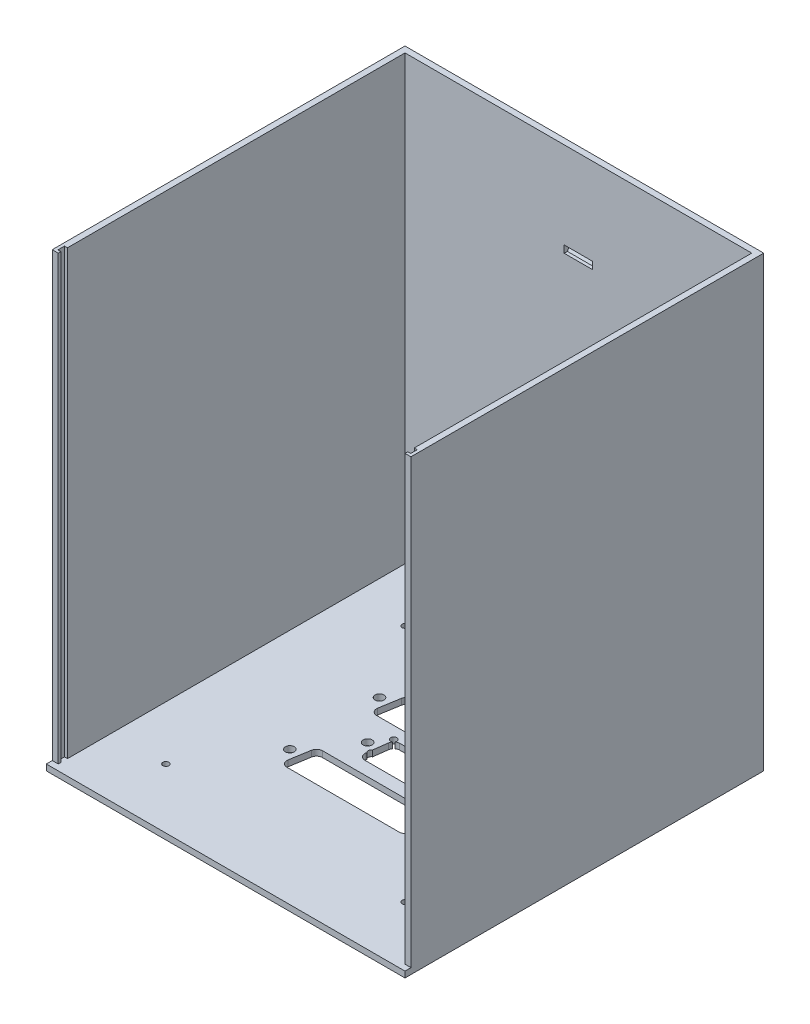
SolidWorks part; units mm, degrees
other "Markup1"
sketch "Sketch8" plane through (60, 0, -60) normal (0.7052, -0.7014, -0.1039) x (0.274, 0.4048, -0.8724)
other "Markup2"
sketch "Sketch9" plane through (60, 0, -60) normal (0.9922, -0.0018, -0.1244) x (-0.0942, 0.6423, -0.7606)
ref_plane "Front Plane" through (0, 0, 0) normal (0, 0, 1) x (1, 0, 0)
ref_plane "Top Plane" through (0, 0, 0) normal (0, 1, 0) x (1, 0, 0)
ref_plane "Right Plane" through (0, 0, 0) normal (1, 0, 0) x (0, 0, -1)
sketch "Sketch1" plane through (0, 0, 0) normal (0, 1, 0) x (1, 0, 0)
  line L5 (-60, 60) -> (60, 60)
  line L6 (-60, 60) -> (-60, -60)
  line L7 (-60, -60) -> (60, -60)
  line L8 (60, 60) -> (60, -60)
  dimension "D1" = 120
  dimension "D2" = 120
  dimension "D3" = 60
  dimension "D4" = 60
extrude "Main-Body" add sketch "Sketch1" along normal blind 150
sketch "Sketch11" plane through (0, 150, 0) normal (0, 1, 0) x (1, 0, 0)
  line L0 (-60, 60) -> (-60, -60) construction
  line L1 (58, -60) -> (-58, -60)
  line L2 (58, -60) -> (58, 58)
  line L3 (58, 58) -> (-58, 58)
  line L4 (-58, -60) -> (-58, 58)
  line L5 (58, -60) -> (-58, 58) construction
  line L6 (58, 58) -> (-58, -60) construction
  line L13 (60, 60) -> (-60, 60) construction
  point P0 (0, -1)
  dimension "D1" = 116
  dimension "D2" = 118
  dimension "D6" = 2
  dimension "D7" = 2
extrude "Hollow" cut sketch "Sketch11" against normal blind 148
sketch "Sketch12" plane through (0, 150, 0) normal (0, 1, 0) x (1, 0, 0)
  line L0 (-60, 60) -> (-60, -60) construction
  line L1 (-58, -60) -> (-60, -60)
  line L2 (-58, -60) -> (-58, -58)
  line L3 (-58, -58) -> (-60, -58)
  line L4 (-60, -60) -> (-60, -58)
  dimension "D1" = 2
extrude "Lid-Cut" cut sketch "Sketch12" against normal blind 148
mirror "Mirror-Lid-Cut" about plane through (0, 0, 0) normal (1, 0, 0) of "Lid-Cut"
sketch "Sketch13" plane through (0, 150, 0) normal (0, 1, 0) x (1, 0, 0)
  line L0 (-58, 58) -> (-58, -58) construction
  line L1 (-58, -57.1) -> (-59, -57.1)
  line L2 (-58, -57.1) -> (-58, -54.9)
  line L3 (-58, -54.9) -> (-59, -54.9)
  line L4 (-59, -57.1) -> (-59, -54.9)
  line L5 (-58, -58) -> (-60, -58) construction
  dimension "D1" = 1
  dimension "D2" = 0.9
  dimension "D3" = 2.2
extrude "Rail-Cut" cut sketch "Sketch13" against normal blind 148
sketch "Sketch2" plane through (0, 0, 0) normal (0, -1, 0) x (1, 0, 0)
  circle A0 centre (-40, 40) radius 1
  circle A1 centre (40, 40) radius 1
  circle A2 centre (40, -40) radius 1
  circle A3 centre (-40, -40) radius 1
  dimension "D1" = 40
  dimension "D3" = 2
  dimension "D2" = 40
  dimension "D4" = 2
  dimension "D5" = 2
extrude "Main-PCB-Holes" cut sketch "Sketch2" against normal up to next
sketch "Sketch3" plane through (0, 150, 0) normal (0, 1, 0) x (1, 0, 0)
  line L0 (-9, 5.23) -> (9, 5.23) construction
  circle A0 centre (-9, 5.23) radius 1.05
  circle A1 centre (9, 5.23) radius 1.05
  circle A2 centre (9, -2.27) radius 1.05
  circle A3 centre (-9, -2.27) radius 1.05
  dimension "D1" = 9
  dimension "D3" = 2.1
  dimension "D2" = 5.23
  dimension "D4" = 2
  dimension "D6" = 18
  dimension "D7" = 7.5
  dimension "D5" = 2
extrude "LED-PCB-Holes" cut sketch "Sketch3" against normal up to next
sketch "Sketch4" plane through (0, 0, 0) normal (0, -1, 0) x (1, 0, 0)
  line L0 (-12.5, 0) -> (12.5, 0) construction
  line L1 (-23.52, -15) -> (23.52, -15) construction
  line L2 (-6.8916, -5.1179) -> (6.8916, -5.1179)
  line L4 (-7.7666, 5.6321) -> (7.7666, 5.6321)
  line L6 (-17.6522, -20.0462) -> (17.6522, -20.0462)
  line L8 (-18.7772, -9.2962) -> (18.7772, -9.2962)
  line L10 (-23.52, 15) -> (23.52, 15) construction
  line L11 (-17.6522, 9.9538) -> (17.6522, 9.9538)
  line L13 (-18.7772, 20.7038) -> (18.7772, 20.7038)
  line L16 (-19.625, 11.625) -> (-20.75, 18.375)
  line L19 (20.75, 18.375) -> (19.625, 11.625)
  line L22 (-8.875, -3.375) -> (-9.75, 3.375)
  line L25 (9.75, 3.375) -> (8.875, -3.375)
  line L28 (-20.75, -11.625) -> (-19.625, -18.375)
  line L31 (19.625, -18.375) -> (20.75, -11.625)
  circle A0 centre (-12.5, 0) radius 1.5
  circle A1 centre (12.5, 0) radius 1.5
  circle A2 centre (-23.52, -15) radius 1.5
  circle A3 centre (23.52, -15) radius 1.5
  circle A4 centre (-23.52, 15) radius 1.5
  circle A5 centre (23.52, 15) radius 1.5
  arc A6 (18.7772, 20.7038) -> (20.75, 18.375) centre (18.7772, 18.7038) cw
  arc A7 (-18.7772, 20.7038) -> (-20.75, 18.375) centre (-18.7772, 18.7038) ccw
  arc A8 (17.6522, 9.9538) -> (19.625, 11.625) centre (17.6522, 11.9538) ccw
  arc A9 (-17.6522, 9.9538) -> (-19.625, 11.625) centre (-17.6522, 11.9538) cw
  arc A10 (20.75, -11.625) -> (18.7772, -9.2962) centre (18.7772, -11.2962) ccw
  arc A11 (17.6522, -20.0462) -> (19.625, -18.375) centre (17.6522, -18.0462) ccw
  arc A12 (-19.625, -18.375) -> (-17.6522, -20.0462) centre (-17.6522, -18.0462) ccw
  arc A13 (-20.75, -11.625) -> (-18.7772, -9.2962) centre (-18.7772, -11.2962) cw
  arc A14 (7.7666, 5.6321) -> (9.75, 3.375) centre (7.7666, 3.6321) cw
  arc A15 (8.875, -3.375) -> (6.8916, -5.1179) centre (6.8916, -3.1179) cw
  arc A16 (-8.875, -3.375) -> (-6.8916, -5.1179) centre (-6.8916, -3.1179) ccw
  arc A17 (-9.75, 3.375) -> (-7.7666, 5.6321) centre (-7.7666, 3.6321) cw
  point P4 (0, 0)
  point P12 (0, 5.6321)
  point P17 (0, -15)
  point P24 (0, -20.0462)
  point P29 (0, 15)
  point P32 (0, -5.1179)
  point P34 (0, 9.9538)
  point P35 (0, 20.7038)
  point P36 (0, -9.2962)
  point P38 (20.1875, -15)
  point P41 (9.3125, 0)
  point P42 (20.1875, 15)
  point P52 (21.1381, 20.7038)
  point P59 (19.3465, 9.9538)
  point P66 (21.1381, -9.2962)
  point P69 (19.3465, -20.0462)
  point P76 (10.0426, 5.6321)
  point P79 (8.6491, -5.1179)
  dimension "D1" = 3
  dimension "D2" = 3
  dimension "D8" = 3
  dimension "D7" = 3
  dimension "D14" = 3
  dimension "D15" = 3
  dimension "D4" = 41.5
  dimension "D21" = 2
  dimension "D25" = 2
  dimension "D27" = 2
  dimension "D3" = 25
  dimension "D6" = 10.75
  dimension "D9" = 47.04
  dimension "D13" = 15
  dimension "D16" = 47.04
  dimension "D18" = 10.75
  dimension "D19" = 15
  dimension "D20" = 10.75
  dimension "D28" = 39.25
  dimension "D30" = 41.5
  dimension "D31" = 39.25
  dimension "D32" = 19.5
  dimension "D33" = 17.75
extrude "Connector-Slots" cut sketch "Sketch4" against normal up to next
mirror "Mirror-Rail-Cut" about plane through (0, 0, 0) normal (1, 0, 0) of "Rail-Cut"
sketch "Sketch14" plane through (0, 0, 0) normal (1, 0, 0) x (0, 0, -1)
  line L0 (58, 121) -> (60, 121)
  line L1 (58, 2) -> (58, 150) construction
  line L2 (60, 150) -> (60, 0) construction
  line L3 (60, 121) -> (60, 120.88)
  line L4 (60, 120.88) -> (60, 119.88)
  line L5 (60, 119.88) -> (59.8206, 119.88)
  line L6 (59.8206, 119.88) -> (59.07, 118.58)
  line L7 (59.07, 118.58) -> (58, 118.58)
  line L10 (60, 150) -> (-58, 150) construction
  line L11 (58, 121) -> (58, 118.58)
  dimension "D1" = 29
  dimension "D2" = 0.12
  dimension "D3" = 2.42
  dimension "D4" = 1
  dimension "D5" = 30
  dimension "D6" = 1.07
extrude "Cut-Extrude1" cut sketch "Sketch14" against normal mid plane 9.5
